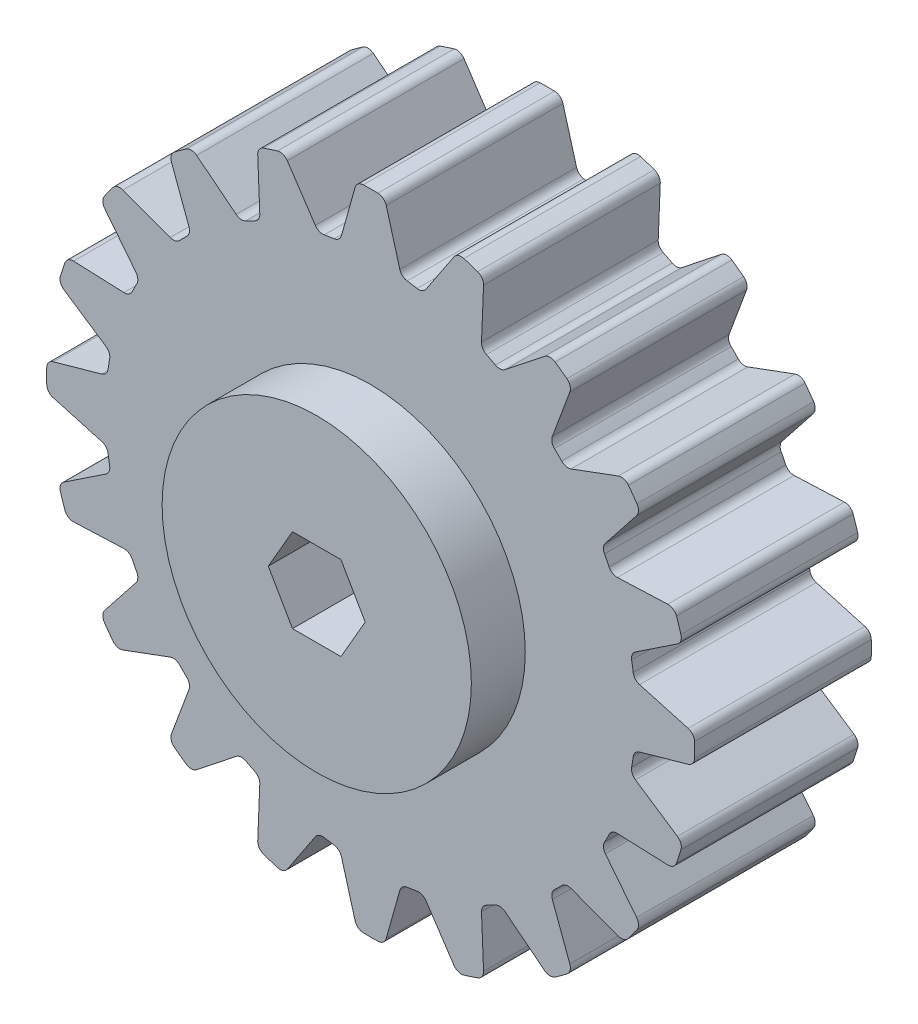
SolidWorks part; units mm, degrees
ref_plane "Front Plane" through (0, 0, 0) normal (0, 0, 1) x (1, 0, 0)
ref_plane "Top Plane" through (0, 0, 0) normal (0, 1, 0) x (1, 0, 0)
ref_plane "Right Plane" through (0, 0, 0) normal (1, 0, 0) x (0, 0, -1)
sketch "Sketch1" plane through (0, 0, 0) normal (0, 0, 1) x (1, 0, 0)
  circle A2 centre (0, 0) radius 9
  dimension "Blank diameter" = 18
extrude "Body" add sketch "Sketch1" against normal blind 6
sketch "Sketch2" plane through (0, 0, 0) normal (0, 0, 1) x (1, 0, 0)
  line L0 (0, 16.3446) -> (0, 3.6554) construction
  line L1 (-0.755, 9.9715) -> (-1.0446, 8.9392)
  line L2 (-0.755, 9.9715) -> (-0.4693, 10.99)
  line L3 (0.755, 9.9715) -> (1.0446, 8.9392)
  line L4 (0.755, 9.9715) -> (0.4693, 10.99)
  line L5 (0, 0) -> (-3.338, 44.0862) construction
  line L6 (0, 0) -> (3.224, 42.5807) construction
  arc A0 (0.4693, 10.99) -> (-0.4693, 10.99) centre (0, 0) ccw
  arc A1 (0.755, 9.9715) -> (-0.755, 9.9715) centre (0, 0) ccw construction
  arc A2 (1.0446, 8.9392) -> (-1.0446, 8.9392) centre (0, 0) ccw
  point P1 (0, 10)
  dimension "D2" = 20
  dimension "D3" = 20
  dimension "Full diameter" = 22
  dimension "Pitch diameter" = 20
  dimension "Blank diameter" = 18
  dimension "Tooth width PCD" = 1.51
extrude "Tooth" add sketch "Sketch2" against normal blind 6
fillet "Tooth Fillet" radius 0.3 4 edges at (-0.4693, 10.99, -3) (-1.0446, 8.9392, -3) (0.4693, 10.99, -3) (1.0446, 8.9392, -3)
pattern_circular "Tooth Pattern" count 20 over 360 about axis through (0, 0, 0) along (0, 0, 1) of "Tooth", "Tooth Fillet"
ref_axis "Axis1" through (0, 0, 0) along (0, 0, -1)
sketch "Sketch3" plane through (0, 0, 0) normal (0, 0, 1) x (1, 0, 0)
  circle A0 centre (0, 0) radius 5.25
  circle A1 centre (0, 0) radius 8
  dimension "Plastic boss" = 10.5
  dimension "Resses" = 16
extrude "Resses1" [suppressed] cut sketch "Sketch3" against normal blind 1
sketch "Sketch4" plane through (0, 0, -6) normal (0, 0, -1) x (-1, 0, 0)
  circle A0 centre (0, 0) radius 8
  circle A1 centre (0, 0) radius 5.25
  dimension "Plastic boss" = 10.5
  dimension "Resses" = 16
extrude "Resses2" cut sketch "Sketch4" against normal blind 1
sketch "Sketch5" plane through (0, 0, -6) normal (0, 0, -1) x (-1, 0, 0)
  circle A0 centre (0, 0) radius 5
  dimension "D1" = 10
extrude "Brass boss" [suppressed] add sketch "Sketch5" along normal blind 5.7
sketch "Sketch6" [suppressed] plane through (0, 0, -11.7) normal (0, 0, -1) x (-1, 0, 0)
  circle A0 centre (0, 0) radius 2
  dimension "D1" = 4
extrude "Bore" [suppressed] cut sketch "Sketch6" against normal through all
sketch "Sketch7" plane through (0, 0, 0) normal (0, 1, 0) x (1, 0, 0)
  circle A0 centre (0, 8.8626) radius 1
  dimension "D1" = 2
extrude "Grub screw" [suppressed] cut sketch "Sketch7" against normal through all
sketch "Sketch8" plane through (0, 0, -5) normal (0, 0, -1) x (-1, 0, 0)
  circle A0 centre (-0.8321, 10.5608) radius 1.8434
extrude "Extrude1" [suppressed] add sketch "Sketch8" along normal blind 5
sketch "Sketch9" plane through (0, 0, -6) normal (0, 0, -1) x (-1, 0, 0)
  circle A0 centre (0, 0) radius 5.25 construction
  circle A1 centre (0, 0) radius 5.25
extrude "Boss-Extrude1" add sketch "Sketch9" along normal blind 1.83 and the other way blind 7.83
sketch "Sketch10" plane through (0, 0, -7.83) normal (0, 0, -1) x (-1, 0, 0)
  line L1 (0.8227, 1.425) -> (-0.8227, 1.425)
  line L2 (-0.8227, 1.425) -> (-1.6454, 0)
  line L3 (-1.6454, 0) -> (-0.8227, -1.425)
  line L4 (-0.8227, -1.425) -> (0.8227, -1.425)
  line L5 (0.8227, -1.425) -> (1.6454, 0)
  line L6 (1.6454, 0) -> (0.8227, 1.425)
  circle A0 centre (0, 0) radius 1.425 construction
  dimension "D1" = 2.85
extrude "Cut-Extrude1" cut sketch "Sketch10" against normal through all
sketch "Sketch11" plane through (0, 0, -5) normal (0, 0, -1) x (-1, 0, 0)
  circle A0 centre (0, 0) radius 5.25 construction
  circle A1 centre (0, 0) radius 8
  circle A2 centre (0, 0) radius 8
  circle A3 centre (0, 0) radius 5.25
  dimension "D1" = 0
extrude "Boss-Extrude2" add sketch "Sketch11" along normal up to surface (1 mm away) up to face at (-8, 0, -6)
